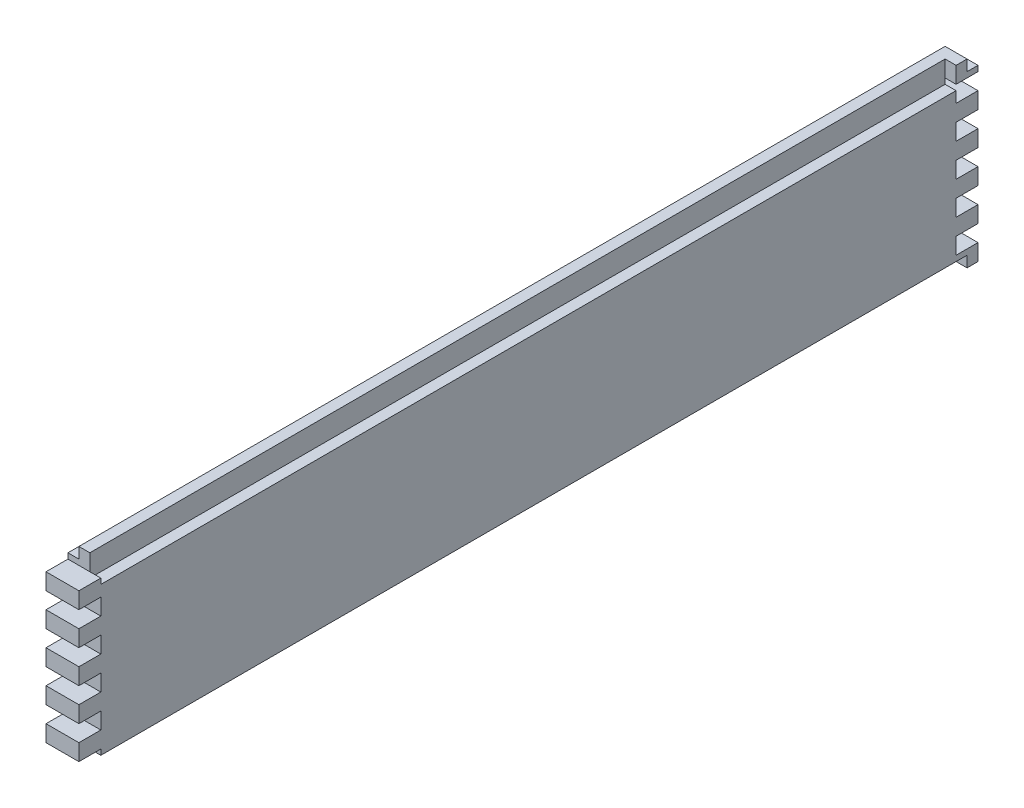
SolidWorks part; units mm, degrees
material "Сосна"
ref_plane "Спереди" through (0, 0, 0) normal (0, 0, 1) x (1, 0, 0)
ref_plane "Сверху" through (0, 0, 0) normal (0, 1, 0) x (1, 0, 0)
ref_plane "Справа" through (0, 0, 0) normal (1, 0, 0) x (0, 0, -1)
sketch "Эскиз1" plane through (0, 0, 0) normal (0, 0, 1) x (1, 0, 0)
  line L0 (0, 0) -> (0, 155)
  line L1 (0, 155) -> (10, 155)
  line L2 (10, 155) -> (10, 165)
  line L3 (10, 165) -> (20, 165)
  line L4 (20, 165) -> (20, 145)
  line L5 (20, 145) -> (30, 145)
  line L6 (30, 145) -> (30, 10)
  line L7 (30, 10) -> (10, 10)
  line L8 (10, 10) -> (10, 0)
  line L9 (10, 0) -> (0, 0)
  dimension "D1" = 10
  dimension "D2" = 10
  dimension "D3" = 10
  dimension "D4" = 10
  dimension "D5" = 20
  dimension "D6" = 10
  dimension "D7" = 10
  dimension "D8" = 155
extrude "Бобышка-Вытянуть1" add sketch "Эскиз1" along normal blind 820
sketch "Эскиз2" plane through (10, 0, 0) normal (1, 0, 0) x (0, 0, -1)
  line L0 (-820, 10) -> (0, 10) construction
  line L1 (-820, 0) -> (-810, 0)
  line L2 (-820, 0) -> (-820, 10)
  line L3 (-820, 10) -> (-810, 10)
  line L4 (-810, 0) -> (-810, 10)
  line L5 (-410, 0) -> (-410, 171.2653) construction
  line L6 (-820, 0) -> (0, 0) construction
  line L7 (-10, 0) -> (-10, 10)
  line L8 (0, 10) -> (-10, 10)
  line L9 (0, 0) -> (0, 10)
  line L10 (0, 0) -> (-10, 0)
  dimension "D1" = 10
extrude "Бобышка-Вытянуть2" add sketch "Эскиз2" along normal up to surface (20 mm away) up to face at (30, 77.5, 410)
sketch "Эскиз4" plane through (20, 0, 0) normal (1, 0, 0) x (0, 0, -1)
  line L0 (-820, 145) -> (0, 145) construction
  line L1 (-820, 165) -> (-800, 165)
  line L2 (-820, 165) -> (-820, 145)
  line L3 (-820, 145) -> (-800, 145)
  line L4 (-800, 165) -> (-800, 145)
  line L5 (-410, 165) -> (-410, 0) construction
  line L6 (-820, 165) -> (0, 165) construction
  line L7 (-20, 165) -> (-20, 145)
  line L8 (0, 145) -> (-20, 145)
  line L9 (0, 165) -> (0, 145)
  line L10 (0, 165) -> (-20, 165)
  dimension "D1" = 20
extrude "Бобышка-Вытянуть3" add sketch "Эскиз4" along normal up to surface (10 mm away) up to face at (30, 38.75, 410)
sketch "Эскиз5" plane through (30, 0, 0) normal (1, 0, 0) x (0, 0, -1)
  line L0 (-410, 145) -> (-410, 0) construction
  line L1 (-820, 165) -> (-810, 165)
  line L2 (-820, 165) -> (-820, 155)
  line L3 (-820, 155) -> (-810, 155)
  line L4 (-810, 165) -> (-810, 155)
  line L5 (-800, 145) -> (-20, 145) construction
  line L6 (-10, 165) -> (-10, 155)
  line L7 (0, 155) -> (-10, 155)
  line L8 (0, 165) -> (0, 155)
  line L9 (0, 165) -> (-10, 165)
  dimension "D1" = 10
  dimension "D2" = 10
extrude "Вырез-Вытянуть2" cut sketch "Эскиз5" against normal through all
sketch "Эскиз6" plane through (0, 0, 0) normal (-1, 0, 0) x (0, 0, 1)
  line L0 (0, 155) -> (0, 0) construction
  line L1 (0, 15) -> (20, 15)
  line L2 (0, 15) -> (0, 30)
  line L3 (0, 30) -> (20, 30)
  line L4 (20, 15) -> (20, 30)
  line L5 (820, 0) -> (0, 0) construction
  dimension "D1" = 15
  dimension "D2" = 15
  dimension "D3" = 20
extrude "Вырез-Вытянуть3" cut sketch "Эскиз6" against normal through all
pattern_linear "Линейный массив1" count 1 spacing 10 along (0, 0, 1) count 5 spacing 30 along (0, 1, 0) of "Вырез-Вытянуть3"
sketch "Эскиз7" plane through (0, 0, 0) normal (-1, 0, 0) x (0, 0, 1)
  line L1 (820, 0) -> (800, 0)
  line L2 (820, 0) -> (820, 15)
  line L3 (820, 15) -> (800, 15)
  line L4 (800, 0) -> (800, 15)
  dimension "D1" = 15
  dimension "D2" = 20
extrude "Вырез-Вытянуть4" cut sketch "Эскиз7" against normal through all
pattern_linear "Линейный массив2" count 1 spacing 10 along (0, 0, -1) count 6 spacing 30 along (0, 1, 0) of "Вырез-Вытянуть4"
